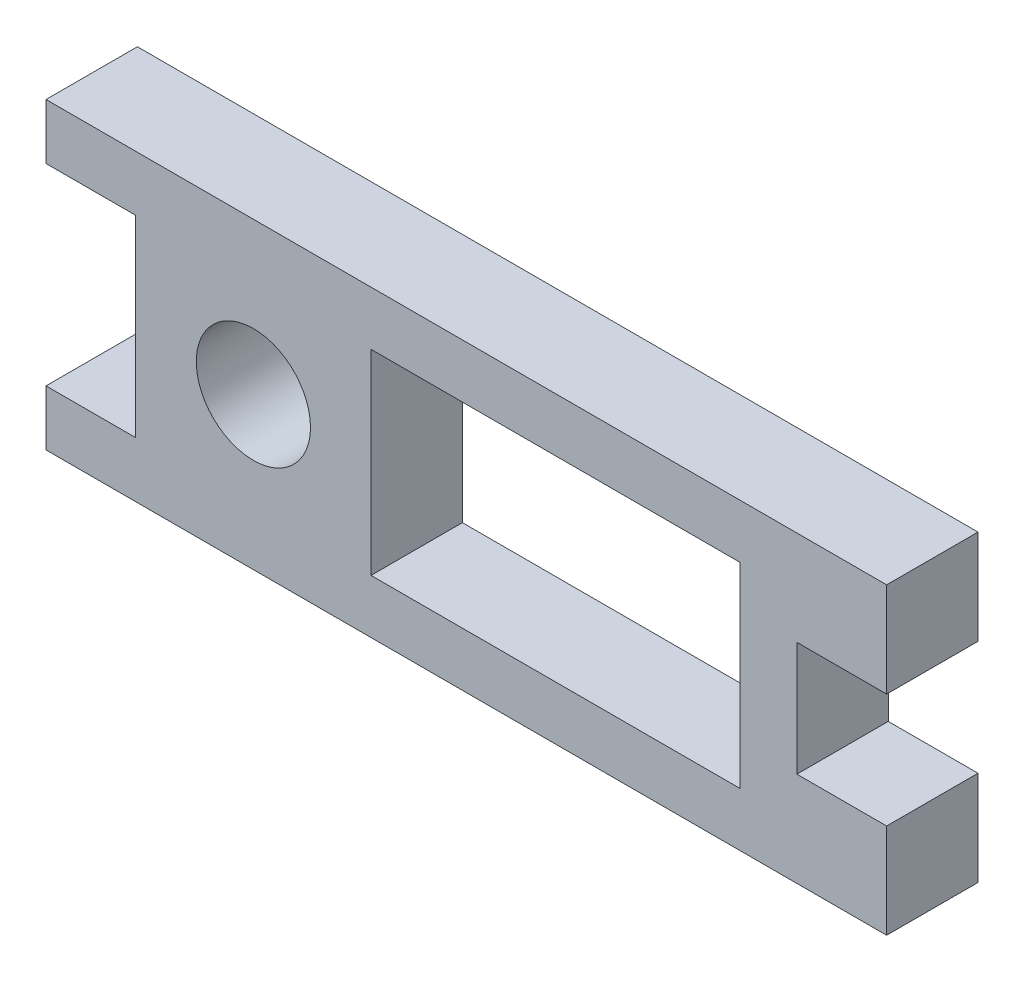
SolidWorks part; units mm, degrees
material "Acrylic (Medium-high impact)"
ref_plane "Front Plane" through (0, 0, 0) normal (0, 0, 1) x (1, 0, 0)
ref_plane "Top Plane" through (0, 0, 0) normal (0, 1, 0) x (1, 0, 0)
ref_plane "Right Plane" through (0, 0, 0) normal (1, 0, 0) x (0, 0, -1)
sketch "Sketch1" plane through (0, 0, 0) normal (0, 0, 1) x (1, 0, 0)
  line L0 (-297.7097, 397.7995) -> (49702.2903, 397.7995) construction
  line L1 (704.2544, 403.6995) -> (704.2544, 391.8995)
  line L2 (704.2544, 403.6995) -> (698.7544, 403.6995)
  line L3 (698.7544, 403.6995) -> (698.7544, 407.0995)
  line L4 (698.7544, 407.0995) -> (750.2744, 407.0995)
  line L5 (750.2744, 407.0995) -> (750.2744, 401.2995)
  line L6 (750.2744, 401.2995) -> (744.7744, 401.2995)
  line L7 (744.7744, 401.2995) -> (744.7744, 394.2995)
  line L8 (744.7744, 394.2995) -> (750.2744, 394.2995)
  line L9 (750.2744, 394.2995) -> (750.2744, 388.4995)
  line L10 (750.2744, 388.4995) -> (698.7544, 388.4995)
  line L11 (698.7544, 388.4995) -> (698.7544, 391.8995)
  line L12 (698.7544, 391.8995) -> (704.2544, 391.8995)
  line L13 (724.5144, 425.1376) -> (724.5144, 373.1851) construction
  line L14 (718.6744, 391.7995) -> (741.2744, 391.7995)
  line L15 (718.6744, 391.7995) -> (718.6744, 403.7995)
  line L16 (718.6744, 403.7995) -> (741.2744, 403.7995)
  line L17 (741.2744, 391.7995) -> (741.2744, 403.7995)
  line L18 (718.6744, 397.7995) -> (704.2544, 397.7995) construction
  line L19 (718.6744, 397.7995) -> (704.2544, 397.7995) construction
  line L20 (718.6744, 397.7995) -> (704.2544, 397.7995) construction
  line L21 (704.2544, 397.7995) -> (711.4644, 397.7995) construction
  line L22 (711.4644, 397.7995) -> (711.4644, 412.076) construction
  circle A0 centre (711.4644, 397.7995) radius 3.5
  point P0 (704.2544, 397.7995)
  point P23 (724.5144, 397.7995)
  dimension "D10" = 7
  dimension "D2" = 3.4
  dimension "D4" = 5.5
  dimension "D5" = 5.5
  dimension "D6" = 5.8
  dimension "D7" = 7
  dimension "D3" = 22.6
  dimension "D8" = 12
  dimension "D9" = 5.84
  dimension "D12" = 14.42
  dimension "D11" = 11.8
extrude "Boss-Extrude1" add sketch "Sketch1" along normal blind 5.6
equation "\"D3@Sketch1\"=\"Servo_length@Servo-1.Part\""
equation "\"D8@Sketch1\"=\"Servo_width@Servo-1.Part\""
equation "\"D9@Sketch1\"=\"Servo_boss_radius@Servo-1.Part\""
